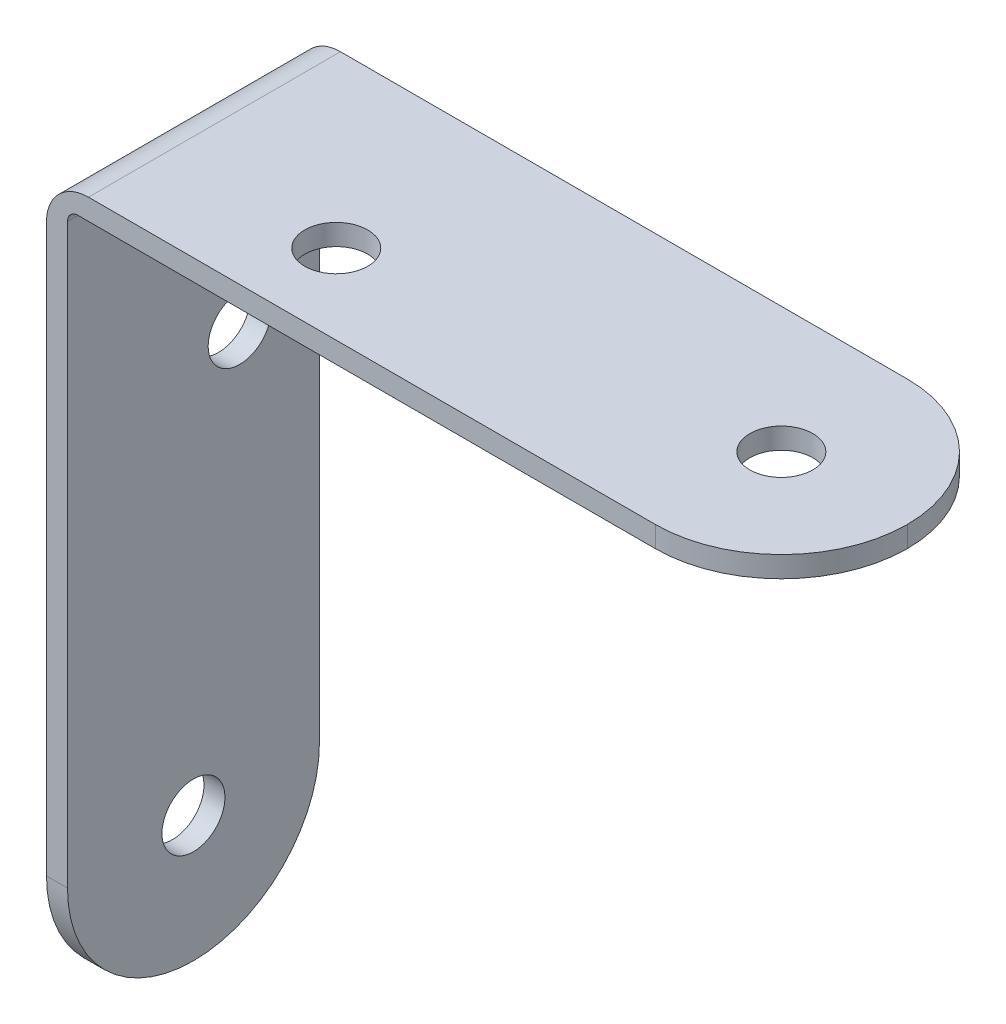
SolidWorks part; units mm, degrees
ref_plane "Front" through (0, 0, 0) normal (0, 0, 1) x (1, 0, 0)
ref_plane "Top" through (0, 0, 0) normal (0, 1, 0) x (1, 0, 0)
ref_plane "Right" through (0, 0, 0) normal (1, 0, 0) x (0, 0, -1)
sketch "草图1" plane through (0, 0, 0) normal (0, 0, 1) x (1, 0, 0)
  line L0 (0, 0) -> (35, 0)
  line L1 (35, 0) -> (35, -1)
  line L2 (35, -1) -> (1, -1)
  line L3 (1, -1) -> (1, -35)
  line L4 (1, -35) -> (0, -35)
  line L5 (0, -35) -> (0, 0)
  dimension "D1" = 1
  dimension "D2" = 0
  dimension "D3" = 1
  dimension "D4" = 35
  dimension "D5" = 35
extrude "凸台-拉伸1" add sketch "草图1" along normal blind 12
fillet "圆角1" radius 6 4 edges at (0.5, -35, 12) (0.5, -35, 0) (35, -0.5, 0) (35, -0.5, 12)
fillet "圆角2" radius 2 1 edges at (0, 0, 6)
fillet "圆角3" radius 0.5 1 edges at (1, -1, 6)
sketch "草图2" plane through (0, 0, 0) normal (-1, 0, 0) x (0, 0, 1)
  line L1 (0, -2) -> (0, -29) construction
  circle A0 centre (6, -29) radius 1.5
  circle A1 centre (3.8, -10) radius 1.5
  dimension "D1" = 3.8
  dimension "D2" = 19
extrude "切除-拉伸1" cut sketch "草图2" against normal through all
sketch "草图3" plane through (0, 0, 0) normal (0, 1, 0) x (1, 0, 0)
  line L0 (29, -12) -> (2, -12) construction
  circle A0 centre (29, -6) radius 1.5
  circle A1 centre (10, -8.2) radius 1.5
  dimension "D1" = 3.8
  dimension "D2" = 19
extrude "切除-拉伸2" cut sketch "草图3" against normal through all
